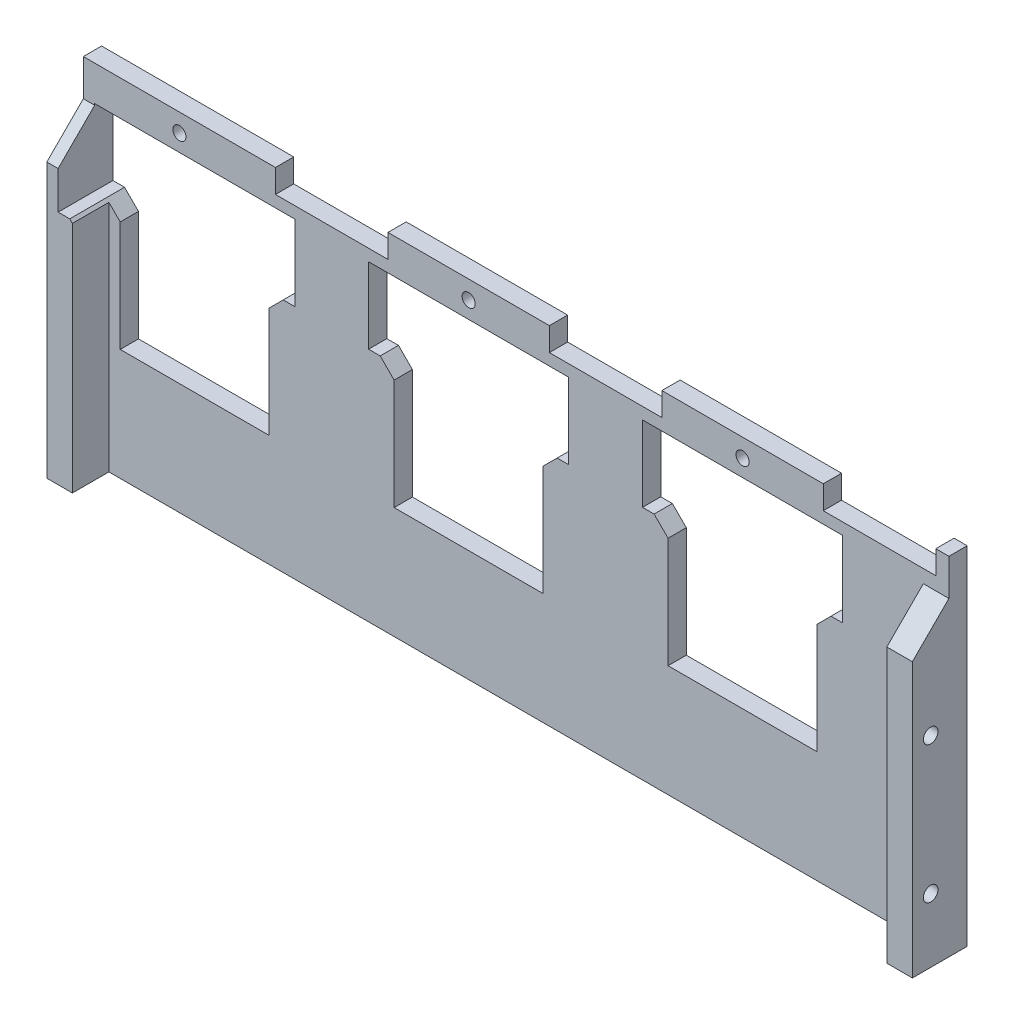
SolidWorks part; units mm, degrees
ref_plane "Płaszczyzna przednia" through (0, 0, 0) normal (0, 0, 1) x (1, 0, 0)
ref_plane "Płaszczyzna górna" through (0, 0, 0) normal (0, 1, 0) x (1, 0, 0)
ref_plane "Płaszczyzna prawa" through (0, 0, 0) normal (1, 0, 0) x (0, 0, -1)
sketch "Szkic1" plane through (0, 0, 0) normal (0, 0, 1) x (1, 0, 0)
  line L1 (-118.5, -72.5) -> (118.5, -72.5)
  line L2 (-118.5, -72.5) -> (-118.5, 72.5)
  line L3 (-118.5, 72.5) -> (118.5, 72.5)
  line L4 (118.5, -72.5) -> (118.5, 72.5)
  line L5 (0, 72.5) -> (0, -72.5) construction
  line L6 (-118.5, 0) -> (118.5, 0) construction
  point P0 (0, 0)
  dimension "D1" = 237
  dimension "D2" = 145
extrude "Dodanie-wyciągnięcie1" add sketch "Szkic1" along normal blind 5
sketch "Szkic2" plane through (0, 0, 5) normal (0, 0, 1) x (1, 0, 0)
  line L0 (118.5, -72.5) -> (118.5, 72.5) construction
  line L1 (118.5, 62.5) -> (111.5, 62.5)
  line L2 (118.5, 62.5) -> (118.5, -72.5)
  line L3 (118.5, -72.5) -> (111.5, -72.5)
  line L4 (111.5, 62.5) -> (111.5, -72.5)
  line L5 (115, -72.5) -> (115, 62.5) construction
  line L6 (118.5, -5) -> (111.5, -5) construction
  line L7 (118.5, 72.5) -> (-118.5, 72.5) construction
  line L9 (0, 0) -> (0, 72.5) construction
  line L10 (-118.5, -5) -> (-111.5, -5) construction
  line L11 (-115, -72.5) -> (-115, 62.5) construction
  line L12 (-111.5, 62.5) -> (-111.5, -72.5)
  line L13 (-118.5, -72.5) -> (-111.5, -72.5)
  line L14 (-118.5, 62.5) -> (-118.5, -72.5)
  line L15 (-118.5, 62.5) -> (-111.5, 62.5)
  line L16 (-118.5, -72.5) -> (118.5, -72.5) construction
  point P20 (-115, -5)
  point P300 (115, -5)
  dimension "D1" = 10
  dimension "D3" = 7
extrude "Dodanie-wyciągnięcie2" add sketch "Szkic2" along normal blind 10
sketch "Szkic3" plane through (118.5, 0, 0) normal (1, 0, 0) x (0, 0, -1)
  line L0 (-10, 62.5) -> (-10, -72.5) construction
  line L1 (-15, 62.5) -> (-5, 62.5) construction
  line L3 (0, -5) -> (-15, -5) construction
  line L5 (-15, -72.5) -> (-15, 62.5) construction
  line L6 (-15, -72.5) -> (-15, 62.5) construction
  line L7 (0, -72.5) -> (0, 72.5) construction
  line L8 (-15, -72.5) -> (0, -72.5) construction
  point P6 (-10, 32.5)
  point P7 (-10, -5)
  point P8 (-10, -42.5)
  point P16 (0, 0)
  point P17 (0, 0)
  point P20 (0, 0)
  point P21 (0, -5)
  point P24 (-10, -72.5)
  dimension "D1" = 37.5
hole_wizard "Otwór Ø4.0 (4)1" positions "Szkic3" profile "Szkic4" hole size "Ø4.0" standard "DIN"
sketch "Szkic4" plane through (118.5, -42.5, 10) normal (0, 1, 0) x (0, 0, -1)
  line L0 (0, 0) -> (0, 6.7)
  line L1 (0, 6.7) -> (2, 6.7)
  line L2 (2, 6.7) -> (2, 0)
  line L5 (2, 0) -> (0, 0)
  line L10 (0, 6.7) -> (-2, 6.7) construction
  line L11 (0, -6.35) -> (0, 107.95) construction
  dimension "Średnica otworu" = 4
  dimension "Głębokość otworu" = 6.7
  dimension "Kąt wiertła" = 180
ref_plane "Płaszczyzna1" through (0, 0, 0) normal (-1, 0, 0) x (0, 0, 1)
mirror "Lustro1" about plane through (0, 0, 0) normal (-1, 0, 0) of "Otwór Ø4.0 (4)1"
chamfer "Sfazowanie1" distance 10 angle 45 2 edges at (-115, 62.5, 15) (115, 62.5, 15)
sketch "Szkic5" plane through (0, 0, 0) normal (0, 0, -1) x (-1, 0, 0)
  line L1 (-86, 42.5546) -> (-86, 42.5)
  line L2 (-84.5, 72.5) -> (-114.5, 72.5)
  line L4 (-11, 42.5546) -> (-11, 42.5)
  line L6 (-9.5, 72.5) -> (-39.5, 72.5)
  line L7 (64, 42.5546) -> (64, 42.5)
  line L12 (-86.2203, 42.1546) -> (-86.2203, 42.1546)
  line L15 (-86.2203, 42.1546) -> (-85.2828, 41.2172)
  line L16 (-85.2828, 41.2172) -> (-82.4, 38.3343)
  line L17 (-82.4, 38.3343) -> (-82.4, 8.1)
  line L22 (-82.4, 8.1) -> (-41.6, 8.1)
  line L39 (-41.6, 8.1) -> (-41.6, 38.3343)
  line L43 (111, 41.5) -> (112, 42.5) construction
  line L44 (-41.6, 38.3343) -> (-38.7172, 41.2172)
  line L46 (112, 42.5) -> (112, 48.5) construction
  line L48 (-38.7172, 41.2172) -> (-37.7797, 42.1546)
  line L49 (108, 38.5) -> (111, 41.5) construction
  line L57 (-37.7797, 42.1546) -> (-37.7797, 42.1546)
  line L58 (61, 62.5) -> (61, 42.5546) construction
  line L59 (61, 42.5546) -> (67.7879, 42.5546) construction
  line L86 (-37.7797, 42.1546) -> (-34.6, 42.1546)
  line L88 (-34.6, 42.1546) -> (-34.6, 62.9)
  line L90 (-34.6, 62.9) -> (-89.4, 62.9)
  line L94 (-89.4, 62.9) -> (-89.4, 42.1546)
  line L102 (-89.4, 42.1546) -> (-86.2203, 42.1546)
  line L103 (-84.1, 72.9) -> (-114.9, 72.9)
  line L104 (108.2121, 42.5546) -> (115, 42.5546) construction
  line L105 (115, 42.5546) -> (115, 62.5) construction
  line L106 (115, 62.5) -> (61, 62.5) construction
  line L109 (64, 42.5) -> (65, 41.5) construction
  line L110 (-114.9, 72.9) -> (-114.9, 66.1)
  line L115 (-114.9, 66.1) -> (-84.1, 66.1)
  line L121 (-84.1, 66.1) -> (-84.1, 72.9)
  line L122 (65, 41.5) -> (68, 38.5) construction
  line L123 (-11.2203, 42.1546) -> (-11.2203, 42.1546)
  line L127 (-11.2203, 42.1546) -> (-10.2828, 41.2172)
  line L128 (-10.2828, 41.2172) -> (-7.4, 38.3343)
  line L129 (-7.4, 38.3343) -> (-7.4, 8.1)
  line L132 (-7.4, 8.1) -> (33.4, 8.1)
  line L134 (33.4, 8.1) -> (33.4, 38.3343)
  line L135 (33.4, 38.3343) -> (36.2828, 41.2172)
  line L168 (36.2828, 41.2172) -> (37.2203, 42.1546)
  line L175 (37.2203, 42.1546) -> (37.2203, 42.1546)
  line L183 (37.2203, 42.1546) -> (40.4, 42.1546)
  line L200 (40.4, 42.1546) -> (40.4, 62.9)
  line L201 (40.4, 62.9) -> (-14.4, 62.9)
  line L206 (-14.4, 62.9) -> (-14.4, 42.1546)
  line L207 (-14.4, 42.1546) -> (-11.2203, 42.1546)
  line L208 (-9.1, 72.9) -> (-39.9, 72.9)
  line L209 (-39.9, 72.9) -> (-39.9, 66.1)
  line L210 (-39.9, 66.1) -> (-9.1, 66.1)
  line L212 (68, 38.5) -> (68, 8.5) construction
  line L213 (68, 8.5) -> (108, 8.5) construction
  line L214 (108, 8.5) -> (108, 38.5) construction
  line L215 (-9.1, 66.1) -> (-9.1, 72.9)
  line L216 (36, 41.5) -> (37, 42.5) construction
  line L225 (37, 42.5) -> (37, 48.5) construction
  line L230 (63.7797, 42.1546) -> (63.7797, 42.1546)
  line L277 (33, 38.5) -> (36, 41.5) construction
  line L278 (63.7797, 42.1546) -> (64.7172, 41.2172)
  line L279 (-14, 62.5) -> (-14, 42.5546) construction
  line L280 (-14, 42.5546) -> (-7.2121, 42.5546) construction
  line L288 (64.7172, 41.2172) -> (67.6, 38.3343)
  line L289 (67.6, 38.3343) -> (67.6, 8.1)
  line L290 (67.6, 8.1) -> (108.4, 8.1)
  line L292 (108.4, 8.1) -> (108.4, 38.3343)
  line L293 (108.4, 38.3343) -> (111.2828, 41.2172)
  line L294 (111.2828, 41.2172) -> (112.2203, 42.1546)
  line L296 (33.2121, 42.5546) -> (40, 42.5546) construction
  line L309 (40, 42.5546) -> (40, 62.5) construction
  line L310 (40, 62.5) -> (-14, 62.5) construction
  line L311 (-11, 42.5) -> (-10, 41.5) construction
  line L312 (112.2203, 42.1546) -> (112.2203, 42.1546)
  line L314 (112.2203, 42.1546) -> (115.4, 42.1546)
  line L318 (115.4, 42.1546) -> (115.4, 62.9)
  line L320 (-10, 41.5) -> (-7, 38.5) construction
  line L333 (115.4, 62.9) -> (60.6, 62.9)
  line L334 (60.6, 62.9) -> (60.6, 42.1546)
  line L335 (60.6, 42.1546) -> (63.7797, 42.1546)
  line L336 (35.1, 72.9) -> (35.1, 66.1)
  line L337 (35.1, 66.1) -> (65.9, 66.1)
  line L338 (65.9, 66.1) -> (65.9, 72.9)
  line L340 (65.9, 72.9) -> (35.1, 72.9)
  line L349 (-7, 38.5) -> (-7, 8.5) construction
  line L350 (-7, 8.5) -> (33, 8.5) construction
  line L351 (33, 8.5) -> (33, 38.5) construction
  line L352 (-42, 38.5) -> (-39, 41.5) construction
  line L355 (-39, 41.5) -> (-38, 42.5) construction
  line L356 (-38, 42.5) -> (-38, 48.5) construction
  line L358 (-86, 42.5) -> (-85, 41.5) construction
  line L362 (-85, 41.5) -> (-82, 38.5) construction
  line L364 (-89, 62.5) -> (-89, 42.5546) construction
  line L365 (-89, 42.5546) -> (-82.2121, 42.5546) construction
  line L373 (-41.7879, 42.5546) -> (-35, 42.5546) construction
  line L374 (-35, 42.5546) -> (-35, 62.5) construction
  line L375 (-35, 62.5) -> (-89, 62.5) construction
  line L391 (-82, 38.5) -> (-82, 8.5) construction
  line L392 (-82, 8.5) -> (-42, 8.5) construction
  line L393 (-42, 8.5) -> (-42, 38.5) construction
  line L395 (35.5, 90.5) -> (35.5, 66.5) construction
  line L396 (35.5, 66.5) -> (65.5, 66.5) construction
  line L397 (65.5, 66.5) -> (65.5, 90.5) construction
  line L399 (-39.5, 90.5) -> (-39.5, 66.5) construction
  line L400 (-39.5, 66.5) -> (-9.5, 66.5) construction
  line L401 (-9.5, 66.5) -> (-9.5, 90.5) construction
  line L402 (-114.5, 90.5) -> (-114.5, 66.5) construction
  line L403 (-114.5, 66.5) -> (-84.5, 66.5) construction
  line L404 (-84.5, 66.5) -> (-84.5, 90.5) construction
  line L407 (111, 41.5) -> (112, 42.5)
  line L408 (112, 42.5) -> (112, 42.5546)
  line L410 (108, 38.5) -> (111, 41.5)
  line L412 (61, 62.5) -> (61, 42.5546)
  line L413 (61, 42.5546) -> (64, 42.5546)
  line L421 (112, 42.5546) -> (115, 42.5546)
  line L422 (115, 42.5546) -> (115, 62.5)
  line L423 (115, 62.5) -> (61, 62.5)
  line L424 (64, 42.5) -> (65, 41.5)
  line L428 (65, 41.5) -> (68, 38.5)
  line L445 (68, 38.5) -> (68, 8.5)
  line L446 (68, 8.5) -> (108, 8.5)
  line L447 (108, 8.5) -> (108, 38.5)
  line L449 (36, 41.5) -> (37, 42.5)
  line L450 (37, 42.5) -> (37, 42.5546)
  line L452 (33, 38.5) -> (36, 41.5)
  line L454 (-14, 62.5) -> (-14, 42.5546)
  line L455 (-14, 42.5546) -> (-11, 42.5546)
  line L463 (37, 42.5546) -> (40, 42.5546)
  line L464 (40, 42.5546) -> (40, 62.5)
  line L465 (40, 62.5) -> (-14, 62.5)
  line L466 (-11, 42.5) -> (-10, 41.5)
  line L470 (-10, 41.5) -> (-7, 38.5)
  line L487 (-7, 38.5) -> (-7, 8.5)
  line L488 (-7, 8.5) -> (33, 8.5)
  line L489 (33, 8.5) -> (33, 38.5)
  line L490 (-42, 38.5) -> (-39, 41.5)
  line L493 (-39, 41.5) -> (-38, 42.5)
  line L494 (-38, 42.5) -> (-38, 42.5546)
  line L496 (-86, 42.5) -> (-85, 41.5)
  line L500 (-85, 41.5) -> (-82, 38.5)
  line L502 (-89, 62.5) -> (-89, 42.5546)
  line L503 (-89, 42.5546) -> (-86, 42.5546)
  line L511 (-38, 42.5546) -> (-35, 42.5546)
  line L512 (-35, 42.5546) -> (-35, 62.5)
  line L513 (-35, 62.5) -> (-89, 62.5)
  line L529 (-82, 38.5) -> (-82, 8.5)
  line L530 (-82, 8.5) -> (-42, 8.5)
  line L531 (-42, 8.5) -> (-42, 38.5)
  line L533 (35.5, 72.5) -> (35.5, 66.5)
  line L534 (35.5, 66.5) -> (65.5, 66.5)
  line L535 (65.5, 66.5) -> (65.5, 72.5)
  line L537 (-39.5, 72.5) -> (-39.5, 66.5)
  line L538 (-39.5, 66.5) -> (-9.5, 66.5)
  line L539 (-9.5, 66.5) -> (-9.5, 72.5)
  line L540 (-114.5, 72.5) -> (-114.5, 66.5)
  line L541 (-114.5, 66.5) -> (-84.5, 66.5)
  line L542 (-84.5, 66.5) -> (-84.5, 72.5)
  line L548 (-118.5, 72.5) -> (-118.5, -72.5)
  line L549 (-118.5, -72.5) -> (118.5, -72.5)
  line L550 (118.5, -72.5) -> (118.5, 72.5)
  line L551 (118.5, 72.5) -> (-118.5, 72.5)
  line L555 (65.5, 72.5) -> (35.5, 72.5)
  point P0 (0, 0)
  line M8 (118.5, 72.5) -> (-118.5, 72.5)
  dimension "D1" = 0
  dimension "D2" = 0.4
extrude "Wytnij-wyciągnięcie1" cut sketch "Szkic5" against normal up to next contours L530 L531 L490 L493 L494 L511 L512 L513 L502 L503 L1 L496 L500 L529 | L541 L542 L540 M8 | L542 L541 L540 L110 L115 L121 M8 | L94 L102 L15 L16 L17 L22 L39 L44 L48 L86 L88 L90 L531 L530 L529 L500 L496 L1 L503 L502 L513 L512 L511 L494 L493 L490 | L488 L489 L452 L449 L450 L463 L464 L465 L454 L455 L4 L466 L470 L487 | L206 L207 L127 L128 L129 L132 L134 L135 L168 L183 L200 L201 L489 L488 L487 L470 L466 L4 L455 L454 L465 L464 L463 L450 L449 L452 | L538 L539 L537 M8 | L539 L538 L537 L209 L210 L215 M8 | L446 L447 L410 L407 L408 L421 L422 L423 L412 L413 L7 L424 L428 L445 | L334 L335 L278 L288 L289 L290 L292 L293 L294 L314 L318 L333 L447 L446 L445 L428 L424 L7 L413 L412 L423 L422 L421 L408 L407 L410 | L534 L535 L533 M8 | L535 L534 L533 L336 L337 L338 M8 region at (62, 37.4744, 0) region at (99.5, 69.5, 0) region at (84.3, 72.1854, 0) region at (39.7, 72.1854, 0) region at (24.5, 69.5, 0) region at (-35.3, 72.1854, 0) region at (-50.5, 69.5, 0) region at (-13, 37.4744, 0) region at (-88, 37.4744, 0) region at (87.8102, 42.2321, 0) region at (12.8102, 42.2321, 0) region at (-62.1898, 42.2321, 0)
ref_plane "Płaszczyzna2" through (0, -22.5, 0) normal (0, -1, 0) x (-1, 0, 0)
split "Podziel1" trim tools "Płaszczyzna2" bodies to split 113 resulting bodies 107 108
sketch "Szkic6" plane through (0, 0, 0) normal (0, 0, -1) x (-1, 0, 0)
  line L3 (-62, 72.5) -> (-62, 67.5) construction
  line L4 (-84.1, 72.5) -> (-39.9, 72.5) construction
  line L6 (13, 72.5) -> (13, 67.5) construction
  line L7 (-9.1, 72.5) -> (35.1, 72.5) construction
  line L9 (92.2, 72.5) -> (92.2, 67.5) construction
  line L10 (65.9, 72.5) -> (118.5, 72.5) construction
  point P18 (-62, 67.5)
  point P20 (13, 67.5)
  point P22 (92.2, 67.5)
  point P44 (0, 0)
  dimension "D1" = 5
hole_wizard "Pogłębienie walcowe pod M3 Śrubę z łbem stożkowym ściętym1" positions "Szkic6" profile "Szkic7" counterbore size "M3" standard "DIN"
sketch "Szkic7" plane through (62, 67.5, 0) normal (1, 0, 0) x (0, 1, 0)
  line L0 (0, 0) -> (0, 7.7815)
  line L1 (0, 7.7815) -> (1.8, 6.7)
  line L2 (1.8, 6.7) -> (1.8, 2.4)
  line L3 (1.8, 2.4) -> (3.5, 2.4)
  line L4 (3.5, 2.4) -> (3.5, 0)
  line L5 (3.5, 0) -> (0, 0)
  line L10 (0, 7.7815) -> (-1.8, 6.7) construction
  line L11 (0, -6.35) -> (0, 107.95) construction
  dimension "Średnica otworu" = 3.6
  dimension "Głębokość otworu" = 6.7
  dimension "Średnica pogłębienia walcowego" = 7
  dimension "Głębokość pogłębienia walcowego" = 2.4
  dimension "Kąt wiertła" = 118
delete or keep bodies "Obiekt-Usuń/zachowaj 1" type delete bodies bodies 108
